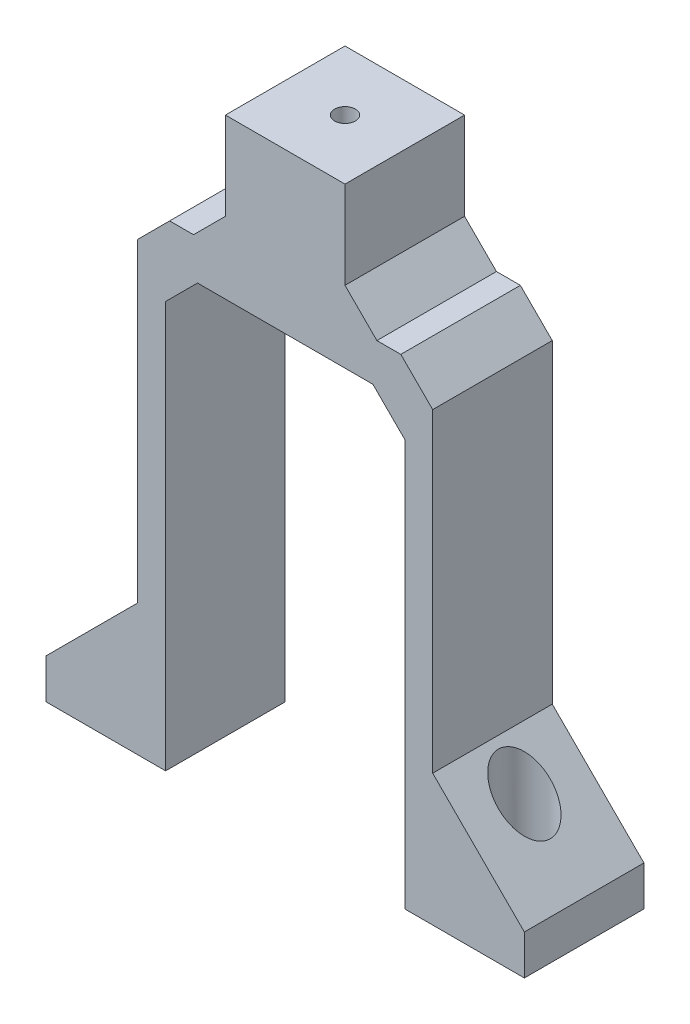
SolidWorks part; units mm, degrees
ref_plane "Front Plane" through (0, 0, 0) normal (0, 0, 1) x (1, 0, 0)
ref_plane "Top Plane" through (0, 0, 0) normal (0, 1, 0) x (1, 0, 0)
ref_plane "Right Plane" through (0, 0, 0) normal (1, 0, 0) x (0, 0, -1)
sketch "Sketch1" plane through (0, 0, 0) normal (0, 1, 0) x (1, 0, 0)
  line L0 (-22.5, 0) -> (22.5, 0) construction
  line L2 (-30, -7.5) -> (-15, -7.5)
  line L3 (-30, -7.5) -> (-30, 7.5)
  line L4 (-30, 7.5) -> (-15, 7.5)
  line L5 (-15, -7.5) -> (-15, 7.5)
  line L6 (-30, -7.5) -> (-15, 7.5) construction
  line L7 (-30, 7.5) -> (-15, -7.5) construction
  line L8 (15, -7.5) -> (30, -7.5)
  line L9 (15, -7.5) -> (15, 7.5)
  line L10 (15, 7.5) -> (30, 7.5)
  line L11 (30, -7.5) -> (30, 7.5)
  line L12 (15, -7.5) -> (30, 7.5) construction
  line L13 (15, 7.5) -> (30, -7.5) construction
  circle A0 centre (-22.5, 0) radius 1.875
  circle A1 centre (22.5, 0) radius 1.875
  point P4 (0, 0)
  dimension "D1" = 3.75
  dimension "D2" = 15
  dimension "D3" = 45
  dimension "D4" = 15
extrude "Boss-Extrude1" add sketch "Sketch1" along normal blind 5
sketch "Sketch2" plane through (0, 5, 0) normal (0, 1, 0) x (1, 0, 0)
  line L0 (-30, -7.5) -> (-15, -7.5) construction
  line L1 (-15, 7.5) -> (-18.5, 7.5)
  line L2 (-15, 7.5) -> (-15, -7.5)
  line L3 (-15, -7.5) -> (-18.5, -7.5)
  line L4 (-18.5, 7.5) -> (-18.5, -7.5)
  line L5 (30, 7.5) -> (15, 7.5) construction
  line L6 (15, -7.5) -> (18.5, -7.5)
  line L7 (15, -7.5) -> (15, 7.5)
  line L8 (15, 7.5) -> (18.5, 7.5)
  line L9 (18.5, -7.5) -> (18.5, 7.5)
  dimension "D1" = 3.5
  dimension "D2" = 3.5
extrude "Boss-Extrude2" add sketch "Sketch2" along normal blind 50
sketch "Sketch4" plane through (0, 55, 0) normal (0, 1, 0) x (1, 0, 0)
  line L1 (-18.5, -7.5) -> (18.5, -7.5)
  line L2 (-18.5, -7.5) -> (-18.5, 7.5)
  line L3 (-18.5, 7.5) -> (18.5, 7.5)
  line L4 (18.5, -7.5) -> (18.5, 7.5)
extrude "Boss-Extrude3" add sketch "Sketch4" along normal blind 5
sketch "Sketch5" plane through (0, 60, 0) normal (0, 1, 0) x (1, 0, 0)
  line L0 (18.5, 7.5) -> (-18.5, 7.5) construction
  line L1 (-7.5, -7.5) -> (7.5, -7.5)
  line L2 (-7.5, -7.5) -> (-7.5, 7.5)
  line L3 (-7.5, 7.5) -> (7.5, 7.5)
  line L4 (7.5, -7.5) -> (7.5, 7.5)
  line L5 (-7.5, -7.5) -> (7.5, 7.5) construction
  line L6 (-7.5, 7.5) -> (7.5, -7.5) construction
  point P0 (0, 0)
extrude "Boss-Extrude4" add sketch "Sketch5" along normal blind 15
sketch "Sketch6" plane through (0, 75, 0) normal (0, 1, 0) x (1, 0, 0)
  circle A0 centre (0, 0) radius 1.3
  dimension "D1" = 2.6
extrude "Cut-Extrude1" cut sketch "Sketch6" against normal through all
chamfer "Chamfer1" distance 4 angle 45 6 edges at (-18.5, 60, 0) (18.5, 60, 0) (7.5, 60, 0) (15, 55, 0) (-15, 55, 0) (-7.5, 60, 0)
sketch "Sketch7" plane through (0, 5, 0) normal (0, 1, 0) x (1, 0, 0)
  circle A0 centre (-22.5, 0) radius 3.25
  circle A1 centre (22.5, 0) radius 3.25
  dimension "D1" = 6.5
extrude "Cut-Extrude2" cut sketch "Sketch7" against normal blind 2
chamfer "Chamfer2" distance 11.5 angle 45 2 edges at (18.5, 5, 0) (-18.5, 5, 0)
